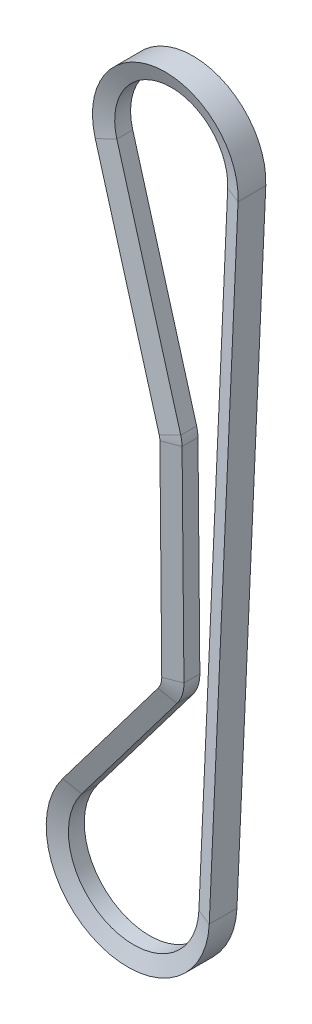
SolidWorks part; units mm, degrees
ref_plane "Front Plane" through (0, 0, 0) normal (0, 0, 1) x (1, 0, 0)
ref_plane "Top Plane" through (0, 0, 0) normal (0, 1, 0) x (1, 0, 0)
ref_plane "Right Plane" through (0, 0, 0) normal (1, 0, 0) x (0, 0, -1)
sketch "Sketch2" plane through (0, 0, 0) normal (0, 0, 1) x (1, 0, 0)
  line L0 (0, 0) -> (1, 0) construction
  line L1 (0, 0) -> (0, 1) construction
  line L12 (24.9747, -1.1245) -> (15.08, -220.8814)
  line L14 (-35.2185, -202.7248) -> (-2.5019, -159.4952)
  line L15 (-1.2156, -155.6046) -> (-1.8609, -85.6076)
  line L16 (-2.1032, -83.9277) -> (-24.0449, -6.8443)
  arc A4 (15.08, -220.8814) -> (-35.2185, -202.7248) centre (-12.8917, -219.622) cw
  arc A7 (-24.0449, -6.8443) -> (24.9747, -1.1245) centre (0, 0) cw
  arc A8 (-2.5019, -159.4952) -> (-1.2156, -155.6046) centre (-7.5653, -155.6632) ccw
  arc A9 (-1.8609, -85.6076) -> (-2.1032, -83.9277) centre (-8.2106, -85.6661) ccw
ref_plane "Plane4" through (-24.0449, -6.8443, 0) normal (-0.2738, 0.9618, 0) x (0.9618, 0.2738, 0)
sketch "Sketch3" plane through (-24.0449, -6.8443, 0) normal (-0.2738, 0.9618, 0) x (0.9618, 0.2738, 0)
  line L0 (0, -4.7625) -> (0, 4.7625)
  line L1 (0, -4.7625) -> (5.588, -2.7286)
  line L2 (5.588, -2.7286) -> (5.588, 2.7286)
  line L3 (5.588, 2.7286) -> (0, 4.7625)
  line L4 (0, 0) -> (5.588, 0) construction
  dimension "D1" = 9.525
  dimension "D2" = 5.588
  dimension "D3" = 40
sweep "Sweep1" add profiles "Sketch3" path "Sketch2"
